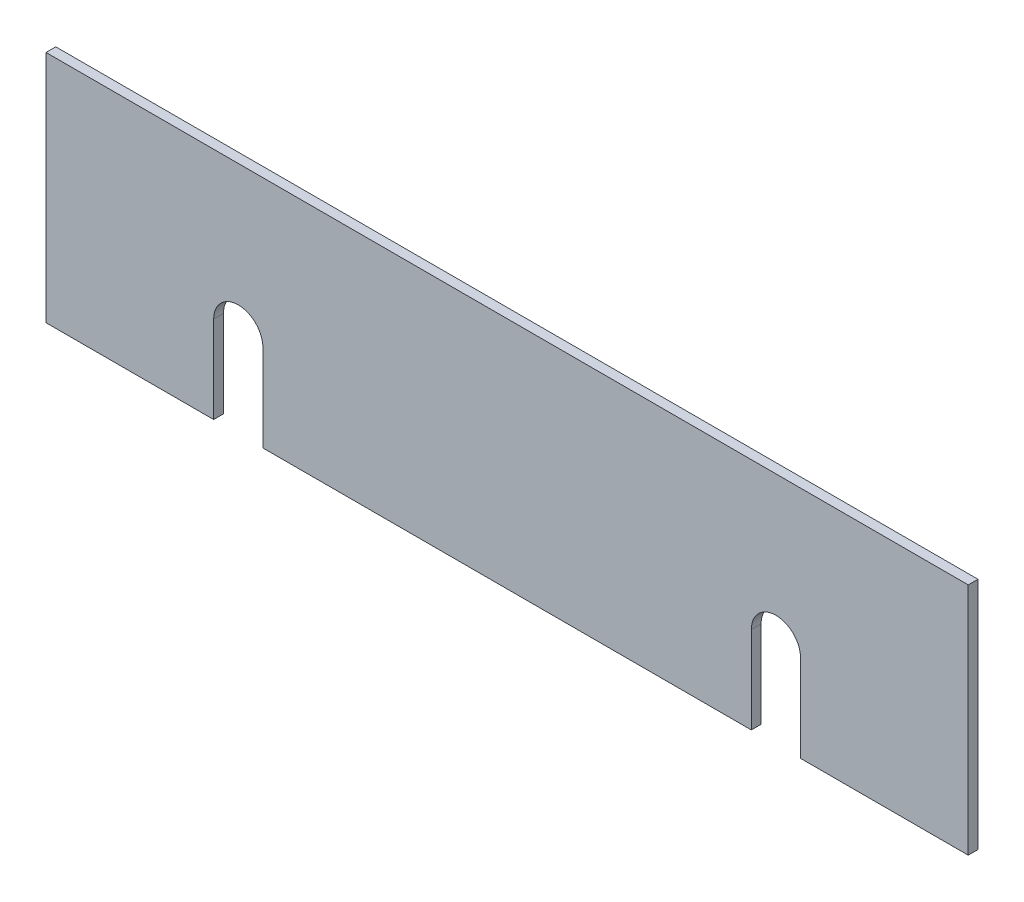
SolidWorks part; units mm, degrees
material "ABS"
ref_plane "X-Y Datum" through (0, 0, 0) normal (0, 0, 1) x (1, 0, 0)
ref_plane "X-Z Datum" through (0, 0, 0) normal (0, 1, 0) x (1, 0, 0)
ref_plane "Y-Z Datum" through (0, 0, 0) normal (1, 0, 0) x (0, 0, -1)
sketch "Sketch1" plane through (0, 0, 0) normal (0, 0, 1) x (1, 0, 0)
  line L1 (-149.85, 38.0375) -> (149.85, 38.0375)
  line L2 (-149.85, 38.0375) -> (-149.85, -38.0375)
  line L3 (-149.85, -38.0375) -> (149.85, -38.0375)
  line L4 (149.85, 38.0375) -> (149.85, -38.0375)
  line L5 (-149.85, 38.0375) -> (149.85, -38.0375) construction
  line L6 (-149.85, -38.0375) -> (149.85, 38.0375) construction
  point P0 (0, 0)
  dimension "D1" = 76.075
  dimension "D2" = 299.7
extrude "Boss-Extrude1" add sketch "Sketch1" along normal blind 3.175
sketch "Sketch3" plane through (0, 0, 0) normal (0, 0, -1) x (-1, 0, 0)
  line L0 (95.3651, -9.7625) -> (95.3651, -38.0375)
  line L1 (149.85, -38.0375) -> (-149.85, -38.0375) construction
  line L2 (79.3651, -9.7625) -> (79.3651, -38.0375)
  line L3 (149.85, -38.0375) -> (-149.85, -38.0375)
  line L4 (-95.3651, -9.7625) -> (-95.3651, -38.0375)
  line L5 (-79.3651, -9.7625) -> (-79.3651, -38.0375)
  circle A0 centre (87.3651, -9.7625) radius 5 construction
  circle A1 centre (-87.3651, -9.7625) radius 5 construction
  circle A2 centre (87.3651, -9.7625) radius 5 construction
  circle A3 centre (-87.3651, -9.7625) radius 5 construction
  circle A4 centre (87.3651, -9.7625) radius 8
  circle A5 centre (-87.3651, -9.7625) radius 8
  line M2 (-149.85, -38.0375) -> (149.85, -38.0375)
  dimension "D1" = 3
extrude "Cut-Extrude1" cut sketch "Sketch3" against normal through all contours A5 A3 | A3 | A5 L4 L3 L5 | A2 | A4 A2 | A4 L2 L0 M2 region at (87.3651, -26.9691, 0) region at (-87.3651, -9.7625, 0) region at (-87.3651, -26.9691, 0) region at (87.3651, -9.7625, 0)
